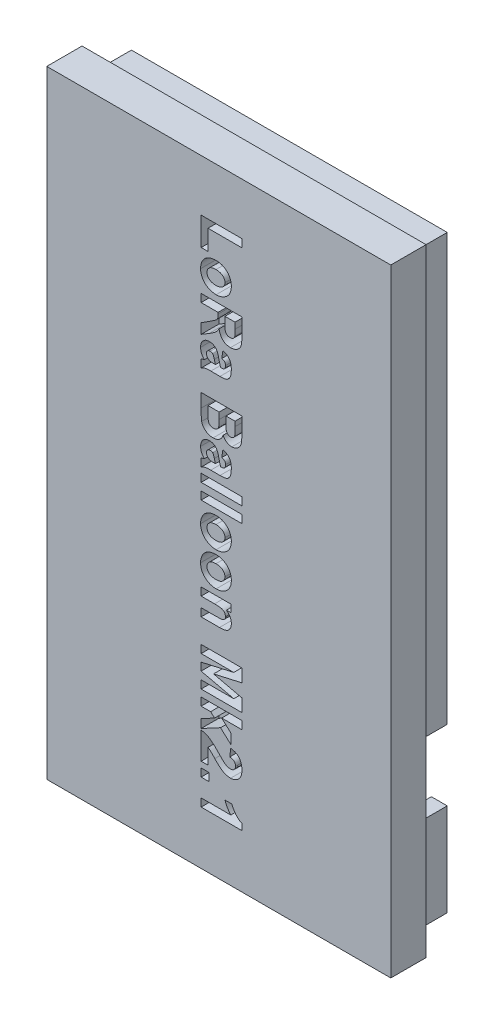
SolidWorks part; units mm, degrees
ref_plane "Front Plane" through (0, 0, 0) normal (0, 0, 1) x (1, 0, 0)
ref_plane "Top Plane" through (0, 0, 0) normal (0, 1, 0) x (1, 0, 0)
ref_plane "Right Plane" through (0, 0, 0) normal (1, 0, 0) x (0, 0, -1)
sketch "Sketch1" plane through (0, 0, 0) normal (0, 0, 1) x (1, 0, 0)
  line L1 (0, 0) -> (39, 0)
  line L2 (0, 0) -> (0, 70)
  line L3 (0, 70) -> (39, 70)
  line L4 (39, 0) -> (39, 70)
  dimension "D1" = 70
  dimension "D2" = 39
extrude "Base" add sketch "Sketch1" along normal blind 4
sketch "Sketch2" plane through (0, 0, 0) normal (0, 0, -1) x (-1, 0, 0)
  line L0 (-39, 0) -> (-39, 70) construction
  line L1 (-37.4, 68.4) -> (-35.6, 68.4)
  line L2 (-37.4, 68.4) -> (-37.4, 1.6)
  line L3 (-37.4, 1.6) -> (-35.6, 1.6)
  line L4 (-35.6, 68.4) -> (-35.6, 1.6)
  line L5 (0, 0) -> (-39, 0) construction
  line L6 (0, 70) -> (0, 0) construction
  line L7 (-35.6, 1.6) -> (-1.6, 1.6)
  line L8 (-35.6, 1.6) -> (-35.6, 3.4)
  line L9 (-35.6, 3.4) -> (-1.6, 3.4)
  line L10 (-1.6, 1.6) -> (-1.6, 3.4)
  line L12 (-39, 70) -> (0, 70) construction
  line L13 (-39, 35) -> (0, 35) construction
  line L14 (-19.5, 70) -> (-19.5, 0) construction
  line L15 (-35.6, 66.6) -> (-1.6, 66.6)
  line L16 (-1.6, 68.4) -> (-1.6, 66.6)
  line L17 (-35.6, 68.4) -> (-1.6, 68.4)
  line L18 (-35.6, 68.4) -> (-35.6, 66.6)
  line L19 (-1.6, 1.6) -> (-3.4, 1.6)
  line L20 (-3.4, 68.4) -> (-3.4, 1.6)
  line L21 (-1.6, 68.4) -> (-3.4, 68.4)
  line L22 (-1.6, 68.4) -> (-1.6, 1.6)
  dimension "D1" = 1.6
  dimension "D2" = 1.8
  dimension "D3" = 1.6
  dimension "D4" = 1.8
extrude "Mount" add sketch "Sketch2" along normal blind 4 contours L4 L1 L2 L3 | L22 L15 L20 L9 | L20 L9 L4 L7 | L9 L20 L7 L10 | L17 L20 L15 L16 | L20 L17 L4 L15 region at (36.5, 35, 0) region at (19.5, 67.5, 0) region at (2.5, 67.5, 0) region at (19.5, 2.5, 0) region at (2.5, 35, 0) region at (2.5, 2.5, 0)
sketch "Sketch3" plane through (0, 0, 4) normal (0, 0, 1) x (1, 0, 0)
  line L0 (17.5, 0) -> (17.5, 70) construction
  line L1 (19.5, 0) -> (19.5, 5) construction
  line L2 (19.5, 70) -> (19.5, 65) construction
  line L3 (39, 70) -> (0, 70) construction
  line L4 (0, 0) -> (39, 0) construction
  line L6 (0, 70) -> (0, 0) construction
  text T0 "<b>  LoRa Balloon Mk2.1</b>" font "Arial Narrow" height in points 18
  dimension "D1" = 17.5
  dimension "D2" = 70
  dimension "D3" = 5
  dimension "D4" = 5
extrude "Name" cut sketch "Sketch3" against normal blind 2
sketch "Sketch4" plane through (35.6, 0, 0) normal (-1, 0, 0) x (0, 0, 1)
  line L0 (-4, 66.6) -> (-4, 3.4) construction
  line L1 (-4, 12.1) -> (0, 12.1)
  line L2 (-4, 12.1) -> (-4, 20.1)
  line L3 (-4, 20.1) -> (0, 20.1)
  line L4 (0, 12.1) -> (0, 20.1)
  line L5 (0, 66.6) -> (0, 3.4) construction
  line L6 (-4, 3.4) -> (0, 3.4) construction
  dimension "D1" = 8.7
  dimension "D2" = 8
extrude "Cut-Extrude1" cut sketch "Sketch4" against normal blind 1.8
sketch "Sketch5" plane through (0, 1.6, 0) normal (0, -1, 0) x (1, 0, 0)
  line L0 (37.4, -4) -> (1.6, -4) construction
  line L1 (9.1, -4) -> (19.1, -4)
  line L2 (9.1, -4) -> (9.1, 0)
  line L3 (9.1, 0) -> (19.1, 0)
  line L4 (19.1, -4) -> (19.1, 0)
  line L5 (37.4, 0) -> (1.6, 0) construction
  line L6 (1.6, -4) -> (1.6, 0) construction
  dimension "D1" = 7.5
  dimension "D2" = 17.5
extrude "Cut-Extrude2" cut sketch "Sketch5" against normal blind 1.8
